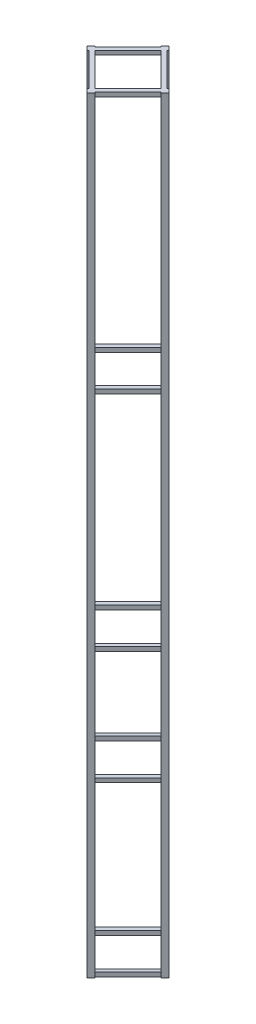
SolidWorks part; units mm, degrees
material "6061-T6 (SS)"
ref_plane "Front Plane" through (0, 0, 0) normal (0, 0, 1) x (1, 0, 0)
ref_plane "Top Plane" through (0, 0, 0) normal (0, 1, 0) x (1, 0, 0)
ref_plane "Right Plane" through (0, 0, 0) normal (1, 0, 0) x (0, 0, -1)
sketch "Sketch2" plane through (0, 0, 0) normal (0, 1, 0) x (1, 0, 0)
  line L0 (0, 94.7743) -> (-8.9803, 85.794)
  line L1 (-8.9803, 85.794) -> (-6.7352, 83.549)
  line L2 (-6.7352, 83.549) -> (0, 90.2842)
  line L3 (0, 90.2842) -> (6.7352, 83.549)
  line L4 (6.7352, 83.549) -> (8.9803, 85.794)
  line L5 (8.9803, 85.794) -> (0, 94.7743)
  line L6 (0, 0) -> (0, 186.644) construction
  line L7 (94.7743, 0) -> (85.794, 8.9803)
  line L8 (85.794, 8.9803) -> (83.549, 6.7352)
  line L9 (83.549, 6.7352) -> (90.2842, 0)
  line L10 (90.2842, 0) -> (83.549, -6.7352)
  line L11 (83.549, -6.7352) -> (85.794, -8.9803)
  line L12 (85.794, -8.9803) -> (94.7743, 0)
  line L13 (0, -94.7743) -> (8.9803, -85.794)
  line L14 (8.9803, -85.794) -> (6.7352, -83.549)
  line L15 (6.7352, -83.549) -> (0, -90.2842)
  line L16 (0, -90.2842) -> (-6.7352, -83.549)
  line L17 (-6.7352, -83.549) -> (-8.9803, -85.794)
  line L18 (-8.9803, -85.794) -> (0, -94.7743)
  line L19 (-94.7743, 0) -> (-85.794, -8.9803)
  line L20 (-85.794, -8.9803) -> (-83.549, -6.7352)
  line L21 (-83.549, -6.7352) -> (-90.2842, 0)
  line L22 (-90.2842, 0) -> (-83.549, 6.7352)
  line L23 (-83.549, 6.7352) -> (-85.794, 8.9803)
  line L24 (-85.794, 8.9803) -> (-94.7743, 0)
  point P31 (0, 0)
  dimension "D2" = 12.7
  dimension "D3" = 12.7
  dimension "D4" = 3.175
  dimension "D5" = 3.175
  dimension "D6" = 4
extrude "Boss-Extrude1" add sketch "Sketch2" along normal blind 1778
sketch "Sketch3" plane through (-45.1421, 0, -45.1421) normal (0.7071, 0, 0.7071) x (0.7071, 0, -0.7071)
  line L0 (-63.8405, 1778) -> (-63.8405, 0) construction
  line L1 (-54.3155, 0) -> (-63.8405, 0)
  line L2 (-54.3155, 0) -> (-54.3155, 9.525)
  line L3 (-54.3155, 9.525) -> (-63.8405, 9.525)
  line L4 (-63.8405, 0) -> (-63.8405, 9.525)
  dimension "D1" = 9.525
extrude "Boss-Extrude2" add sketch "Sketch3" along normal up to next (127.6811 mm away)
sketch "Sketch4" plane through (45.1421, 0, 45.1421) normal (-0.7071, 0, -0.7071) x (-0.7071, 0, 0.7071)
  line L0 (-54.3155, 1778) -> (-54.3155, 0) construction
  line L1 (-63.8405, 0) -> (-54.3155, 0)
  line L2 (-63.8405, 0) -> (-63.8405, 9.525)
  line L3 (-63.8405, 9.525) -> (-54.3155, 9.525)
  line L4 (-54.3155, 0) -> (-54.3155, 9.525)
  dimension "D1" = 9.525
extrude "Boss-Extrude3" add sketch "Sketch4" along normal up to next (127.6811 mm away)
sketch "Sketch5" plane through (38.4069, 0, -38.4069) normal (-0.7071, 0, 0.7071) x (0.7071, 0, 0.7071)
  line L0 (-67.0155, 0) -> (67.0155, 0) construction
  line L1 (-63.8405, 9.525) -> (-54.3155, 9.525)
  line L2 (-63.8405, 9.525) -> (-63.8405, 0)
  line L3 (-63.8405, 0) -> (-54.3155, 0)
  line L4 (-54.3155, 9.525) -> (-54.3155, 0)
  dimension "D1" = 9.525
extrude "Boss-Extrude4" add sketch "Sketch5" along normal up to next (108.6311 mm away)
sketch "Sketch6" plane through (-38.4069, 0, 38.4069) normal (0.7071, 0, -0.7071) x (-0.7071, 0, -0.7071)
  line L0 (-67.0155, 0) -> (54.3155, 0) construction
  line L1 (-63.8405, 9.525) -> (-54.3155, 9.525)
  line L2 (-63.8405, 9.525) -> (-63.8405, 0)
  line L3 (-63.8405, 0) -> (-54.3155, 0)
  line L4 (-54.3155, 9.525) -> (-54.3155, 0)
  dimension "D1" = 9.525
extrude "Boss-Extrude5" add sketch "Sketch6" along normal up to next
sketch "Sketch7" plane through (45.1421, 0, 45.1421) normal (-0.7071, 0, -0.7071) x (-0.7071, 0, 0.7071)
  line L0 (54.3155, 9.525) -> (54.3155, 390.525) construction
  line L1 (54.3155, 1778) -> (54.3155, 9.525) construction
  line L2 (63.8405, 1778) -> (63.8405, 9.525) construction
  line L3 (54.3155, 390.525) -> (63.8405, 390.525)
  line L4 (54.3155, 390.525) -> (54.3155, 400.05)
  line L5 (54.3155, 400.05) -> (63.8405, 400.05)
  line L6 (63.8405, 390.525) -> (63.8405, 400.05)
  dimension "D1" = 381
  dimension "D2" = 9.525
extrude "Boss-Extrude6" add sketch "Sketch7" along normal up to next
sketch "Sketch8" plane through (-38.4069, 0, 38.4069) normal (0.7071, 0, -0.7071) x (-0.7071, 0, -0.7071)
  line L0 (63.8405, 390.525) -> (-63.8405, 390.525) construction
  line L1 (-63.8405, 400.05) -> (-54.3155, 400.05)
  line L2 (-63.8405, 400.05) -> (-63.8405, 390.525)
  line L3 (-63.8405, 390.525) -> (-54.3155, 390.525)
  line L4 (-54.3155, 400.05) -> (-54.3155, 390.525)
  dimension "D1" = 9.525
extrude "Boss-Extrude7" add sketch "Sketch8" along normal up to next
sketch "Sketch9" plane through (38.4069, 0, 38.4069) normal (-0.7071, 0, -0.7071) x (-0.7071, 0, 0.7071)
  line L0 (-63.8405, 390.525) -> (54.3155, 390.525) construction
  line L1 (-63.8405, 400.05) -> (-54.3155, 400.05)
  line L2 (-63.8405, 400.05) -> (-63.8405, 390.525)
  line L3 (-63.8405, 390.525) -> (-54.3155, 390.525)
  line L4 (-54.3155, 400.05) -> (-54.3155, 390.525)
  dimension "D1" = 9.525
extrude "Boss-Extrude8" add sketch "Sketch9" along normal up to next
sketch "Sketch10" plane through (38.4069, 0, -38.4069) normal (-0.7071, 0, 0.7071) x (0.7071, 0, 0.7071)
  line L0 (-63.8405, 390.525) -> (54.3155, 390.525) construction
  line L1 (-63.8405, 400.05) -> (-54.3155, 400.05)
  line L2 (-63.8405, 400.05) -> (-63.8405, 390.525)
  line L3 (-63.8405, 390.525) -> (-54.3155, 390.525)
  line L4 (-54.3155, 400.05) -> (-54.3155, 390.525)
  dimension "D1" = 9.525
extrude "Boss-Extrude9" add sketch "Sketch10" along normal up to next
sketch "Sketch11" plane through (-45.1421, 0, -45.1421) normal (0.7071, 0, 0.7071) x (0.7071, 0, -0.7071)
  line L0 (-63.8405, 400.05) -> (-63.8405, 654.05) construction
  line L1 (-63.8405, 1778) -> (-63.8405, 400.05) construction
  line L2 (-54.3155, 1778) -> (-54.3155, 400.05) construction
  line L3 (-63.8405, 654.05) -> (-54.3155, 654.05)
  line L4 (-63.8405, 654.05) -> (-63.8405, 663.575)
  line L5 (-63.8405, 663.575) -> (-54.3155, 663.575)
  line L6 (-54.3155, 654.05) -> (-54.3155, 663.575)
  dimension "D1" = 254
  dimension "D2" = 9.525
extrude "Boss-Extrude10" add sketch "Sketch11" along normal up to next
sketch "Sketch12" plane through (-38.4069, 0, 38.4069) normal (0.7071, 0, -0.7071) x (-0.7071, 0, -0.7071)
  line L0 (-63.8405, 654.05) -> (63.8405, 654.05) construction
  line L1 (-63.8405, 663.575) -> (-54.3155, 663.575)
  line L2 (-63.8405, 663.575) -> (-63.8405, 654.05)
  line L3 (-63.8405, 654.05) -> (-54.3155, 654.05)
  line L4 (-54.3155, 663.575) -> (-54.3155, 654.05)
  dimension "D1" = 9.525
extrude "Boss-Extrude11" add sketch "Sketch12" along normal up to next
sketch "Sketch13" plane through (38.4069, 0, 38.4069) normal (-0.7071, 0, -0.7071) x (-0.7071, 0, 0.7071)
  line L0 (-63.8405, 654.05) -> (54.3155, 654.05) construction
  line L1 (-63.8405, 663.575) -> (-54.3155, 663.575)
  line L2 (-63.8405, 663.575) -> (-63.8405, 654.05)
  line L3 (-63.8405, 654.05) -> (-54.3155, 654.05)
  line L4 (-54.3155, 663.575) -> (-54.3155, 654.05)
  dimension "D1" = 9.525
extrude "Boss-Extrude12" add sketch "Sketch13" along normal up to next
sketch "Sketch14" plane through (38.4069, 0, -38.4069) normal (-0.7071, 0, 0.7071) x (0.7071, 0, 0.7071)
  line L0 (-63.8405, 654.05) -> (54.3155, 654.05) construction
  line L1 (-63.8405, 663.575) -> (-54.3155, 663.575)
  line L2 (-63.8405, 663.575) -> (-63.8405, 654.05)
  line L3 (-63.8405, 654.05) -> (-54.3155, 654.05)
  line L4 (-54.3155, 663.575) -> (-54.3155, 654.05)
  dimension "D1" = 9.525
extrude "Boss-Extrude13" add sketch "Sketch14" along normal up to next
sketch "Sketch15" plane through (45.1421, 0, -45.1421) normal (-0.7071, 0, 0.7071) x (0.7071, 0, 0.7071)
  line L0 (-63.8405, 663.575) -> (-63.8405, 1171.575) construction
  line L1 (-63.8405, 1778) -> (-63.8405, 663.575) construction
  dimension "D1" = 508
sketch "Sketch16" plane through (45.1421, 0, -45.1421) normal (-0.7071, 0, 0.7071) x (0.7071, 0, 0.7071)
  line L0 (-54.3155, 1778) -> (-54.3155, 663.575) construction
  line L1 (-63.8405, 1171.575) -> (-54.3155, 1171.575)
  line L2 (-63.8405, 1171.575) -> (-63.8405, 1181.1)
  line L3 (-63.8405, 1181.1) -> (-54.3155, 1181.1)
  line L4 (-54.3155, 1171.575) -> (-54.3155, 1181.1)
  dimension "D1" = 9.525
extrude "Boss-Extrude14" add sketch "Sketch16" along normal up to next
sketch "Sketch17" plane through (-38.4069, 0, -38.4069) normal (0.7071, 0, 0.7071) x (0.7071, 0, -0.7071)
  line L0 (-63.8405, 1171.575) -> (63.8405, 1171.575) construction
  line L1 (-63.8405, 1181.1) -> (-54.3155, 1181.1)
  line L2 (-63.8405, 1181.1) -> (-63.8405, 1171.575)
  line L3 (-63.8405, 1171.575) -> (-54.3155, 1171.575)
  line L4 (-54.3155, 1181.1) -> (-54.3155, 1171.575)
  dimension "D1" = 9.525
extrude "Boss-Extrude15" add sketch "Sketch17" along normal up to next
sketch "Sketch18" plane through (-38.4069, 0, 38.4069) normal (0.7071, 0, -0.7071) x (-0.7071, 0, -0.7071)
  line L0 (-63.8405, 1171.575) -> (54.3155, 1171.575) construction
  line L1 (-63.8405, 1181.1) -> (-54.3155, 1181.1)
  line L2 (-63.8405, 1181.1) -> (-63.8405, 1171.575)
  line L3 (-63.8405, 1171.575) -> (-54.3155, 1171.575)
  line L4 (-54.3155, 1181.1) -> (-54.3155, 1171.575)
  dimension "D1" = 9.525
extrude "Boss-Extrude16" add sketch "Sketch18" along normal up to next
sketch "Sketch19" plane through (38.4069, 0, 38.4069) normal (-0.7071, 0, -0.7071) x (-0.7071, 0, 0.7071)
  line L0 (-63.8405, 1171.575) -> (54.3155, 1171.575) construction
  line L1 (-63.8405, 1181.1) -> (-54.3155, 1181.1)
  line L2 (-63.8405, 1181.1) -> (-63.8405, 1171.575)
  line L3 (-63.8405, 1171.575) -> (-54.3155, 1171.575)
  line L4 (-54.3155, 1181.1) -> (-54.3155, 1171.575)
  dimension "D1" = 9.525
extrude "Boss-Extrude17" add sketch "Sketch19" along normal up to next
sketch "Sketch20" plane through (45.1421, 0, 45.1421) normal (-0.7071, 0, -0.7071) x (-0.7071, 0, 0.7071)
  line L0 (-63.8405, 1181.1) -> (-63.8405, 1790.7) construction
  line L1 (-63.8405, 1181.1) -> (-54.3155, 1181.1) construction
  line L2 (-63.8405, 1778) -> (-63.8405, 1181.1) construction
  dimension "D1" = 609.6
pattern_linear "LPattern1" count 2 spacing 1768.475 along (0, 1, 0) of "Boss-Extrude2", "Boss-Extrude3", "Boss-Extrude4", "Boss-Extrude5"
sketch "Sketch21" plane through (0, 1778, 0) normal (0, 1, 0) x (1, 0, 0)
  circle A0 centre (0, 0) radius 94.7743
sketch "Sketch22" plane through (0, 0, 0) normal (0, -1, 0) x (1, 0, 0)
  circle A0 centre (0, 0) radius 94.7743
